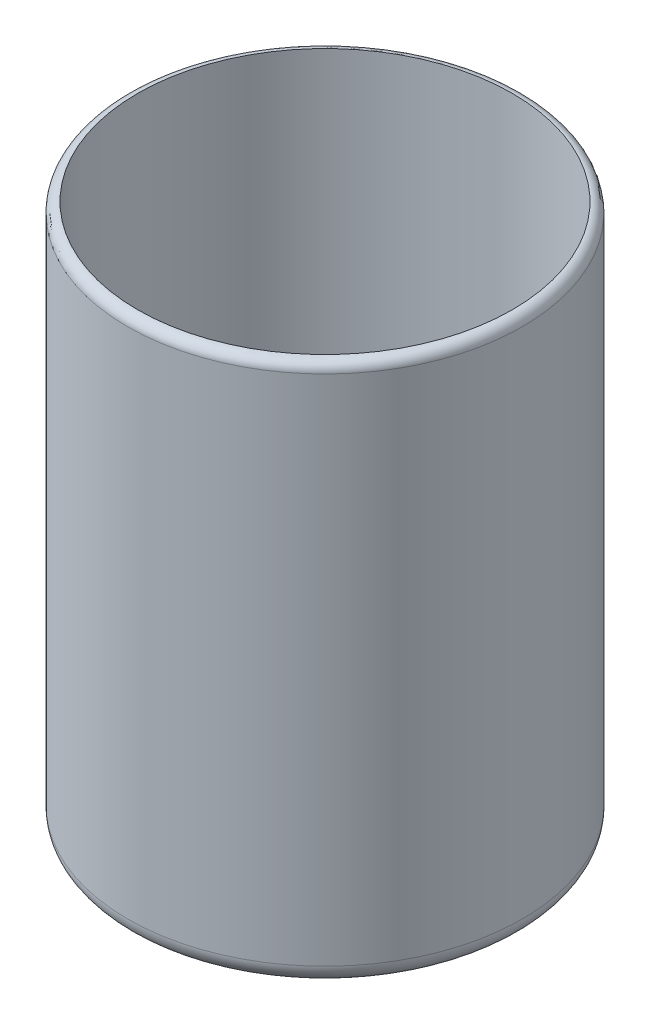
SolidWorks part; units mm, degrees
ref_plane "Front Plane" through (0, 0, 0) normal (0, 0, 1) x (1, 0, 0)
ref_plane "Top Plane" through (0, 0, 0) normal (0, 1, 0) x (1, 0, 0)
ref_plane "Right Plane" through (0, 0, 0) normal (1, 0, 0) x (0, 0, -1)
sketch "Sketch1" plane through (0, 0, 0) normal (0, 1, 0) x (1, 0, 0)
  circle A0 centre (0, 0) radius 20
  dimension "D1" = 40
extrude "Boss-Extrude1" add sketch "Sketch1" along normal blind 55
shell "Shell1" thickness 1 removed face at (0, 55, 20)
fillet "Fillet1" radius 2 1 edges at (0, 0, 20)
fillet "Fillet7" radius 1 1 edges at (0, 55, 20) type face fillet first side face at (0, 55, 19) second side face at (0, 2, 20)
